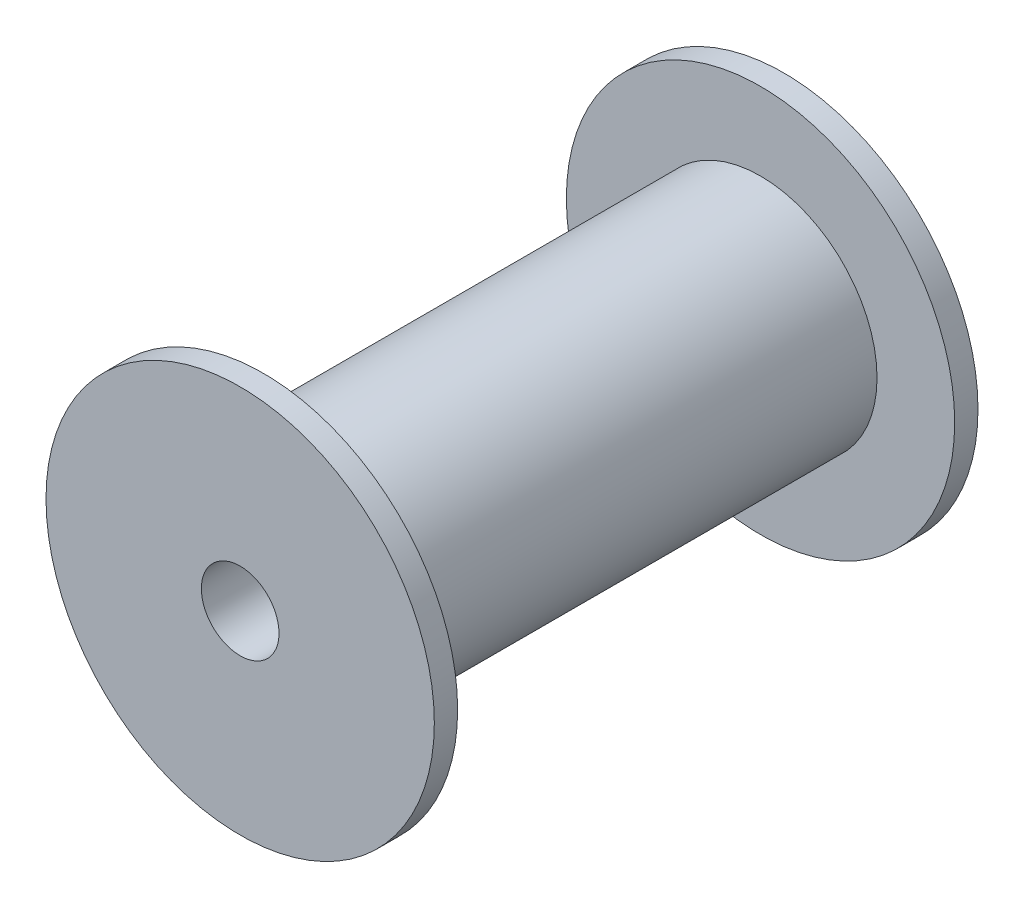
SolidWorks part; units mm, degrees
material "6061-T6 (SS)"
ref_plane "Alzado" through (0, 0, 0) normal (0, 0, 1) x (1, 0, 0)
ref_plane "Planta" through (0, 0, 0) normal (0, 1, 0) x (1, 0, 0)
ref_plane "Vista lateral" through (0, 0, 0) normal (1, 0, 0) x (0, 0, -1)
sketch3d "Sk_Cuerpo"
  line L0 (-425.1, 65, -50) -> (-425.1, 65, 25.5)
sweep "Cuerpo" add path "Sk_Cuerpo" circular profile diameter 30 parameters "D3"=30
sketch3d "Sk_Brida_izq"
  line L0 (-425.1, 65, -44.5) -> (-425.1, 65, -41.5)
sweep "Brida_izq" add path "Sk_Brida_izq" circular profile diameter 50 parameters "D3"=50
sketch3d "Sk_Brida_dcha"
  line L0 (-425.1, 65, 22.5) -> (-425.1, 65, 25.5)
sweep "Brida_dcha" add path "Sk_Brida_dcha" circular profile diameter 50 parameters "D3"=50
sketch3d "Sk_Taladro_eje"
  line L0 (-425.1, 65, -50) -> (-425.1, 65, 25.5)
sweep "Taladro_eje" cut path "Sk_Taladro_eje" circular profile diameter 10 parameters "D3"=10
sketch3d "Sk_Alojamiento_rodamiento_izq"
  line L0 (-425.1, 65, -50) -> (-425.1, 65, -42)
sweep "Alojamiento_rodamiento_izq" cut path "Sk_Alojamiento_rodamiento_izq" circular profile diameter 26 parameters "D3"=26
